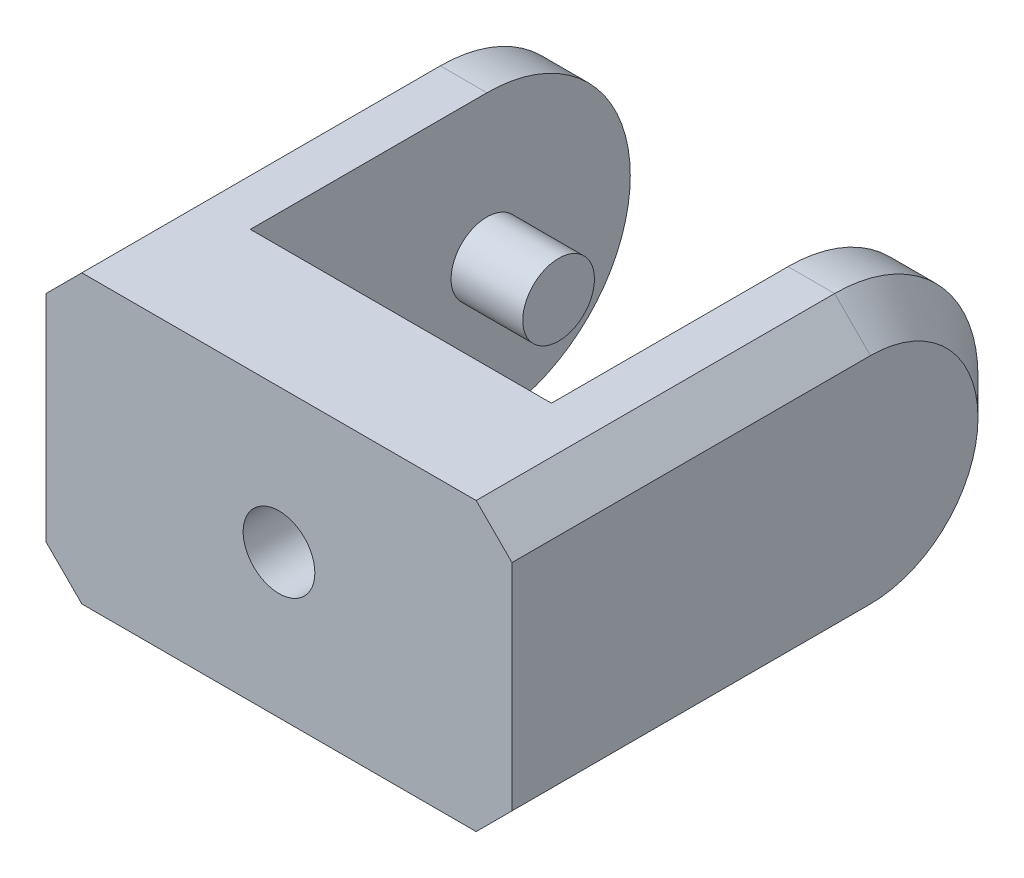
SolidWorks part; units mm, degrees
ref_plane "Front Plane" through (0, 0, 0) normal (0, 0, 1) x (1, 0, 0)
ref_plane "Top Plane" through (0, 0, 0) normal (0, 1, 0) x (1, 0, 0)
ref_plane "Right Plane" through (0, 0, 0) normal (1, 0, 0) x (0, 0, -1)
sketch "Sketch1" plane through (0, 0, 0) normal (0, 0, 1) x (1, 0, 0)
  line L4 (0, 0) -> (65, 0)
  line L5 (0, 0) -> (0, 40)
  line L6 (0, 40) -> (65, 40)
  line L7 (65, 0) -> (65, 40)
  dimension "D1" = 65
  dimension "D2" = 40
extrude "Boss-Extrude1" add sketch "Sketch1" along normal blind 17 contours L4 L7 L6 L5
sketch "Sketch2" plane through (0, 0, 0) normal (0, 0, -1) x (-1, 0, 0)
  line L0 (0, 0) -> (-65, 0) construction
  line L1 (0, 40) -> (-11.5, 40)
  line L2 (0, 40) -> (0, 0)
  line L3 (0, 0) -> (-11.5, 0)
  line L4 (-11.5, 40) -> (-11.5, 0)
  line L6 (-65, 40) -> (-53.5, 40)
  line L7 (-65, 40) -> (-65, 0)
  line L8 (-65, 0) -> (-53.5, 0)
  line L9 (-53.5, 40) -> (-53.5, 0)
  dimension "D1" = 11.5
  dimension "D2" = 11.5
extrude "Boss-Extrude2" add sketch "Sketch2" along normal blind 53
fillet "Fillet1" radius 20 4 edges at (59.25, 40, -53) (5.75, 40, -53) (59.25, 0, -53) (5.75, 0, -53)
chamfer "Chamfer1" distance 5 angle 45 8 edges at (0, 40, -8) (0, 34.1421, -47.1421) (0, 5.8579, -47.1421) (0, 0, -8) (65, 40, -8) (65, 34.1421, -47.1421) (65, 5.8579, -47.1421) (65, 0, -8)
sketch "Sketch3" plane through (0, 0, 17) normal (0, 0, 1) x (1, 0, 0)
  circle A0 centre (32.5, 20) radius 5
  point P2 (0, 0)
  dimension "D1" = 10
extrude "Cut-Extrude1" cut sketch "Sketch3" against normal blind 10
sketch "Sketch4" plane through (11.5, 0, 0) normal (1, 0, 0) x (0, 0, -1)
  circle A0 centre (33, 20) radius 5
  dimension "D1" = 10
extrude "Boss-Extrude3" add sketch "Sketch4" along normal blind 10
